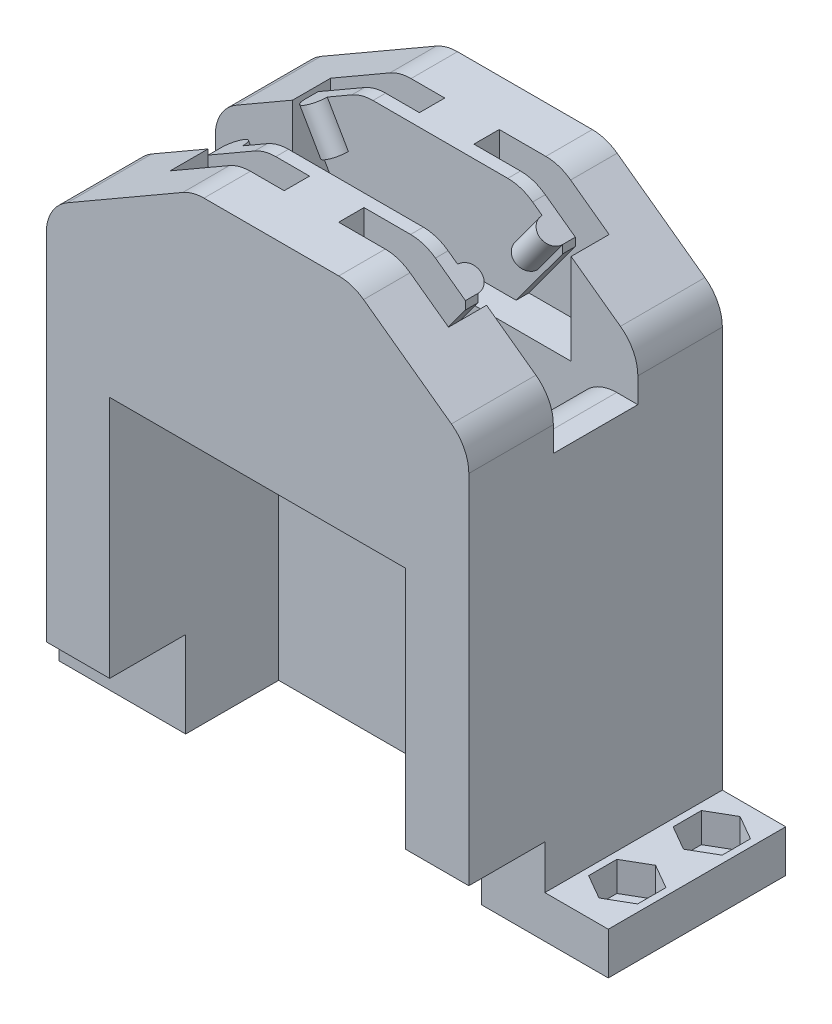
SolidWorks part; units mm, degrees
ref_plane "Front Plane" through (0, 0, 0) normal (0, 0, 1) x (1, 0, 0)
ref_plane "Top Plane" through (0, 0, 0) normal (0, 1, 0) x (1, 0, 0)
ref_plane "Right Plane" through (0, 0, 0) normal (1, 0, 0) x (0, 0, -1)
sketch "Sketch1" plane through (0, 0, 0) normal (0, 0, 1) x (1, 0, 0)
  line L0 (0.5834, 17.8723) -> (-16.7371, 7.8723)
  line L1 (-16.7371, 17.8723) -> (33.2629, 17.8723)
  line L2 (-16.7371, 17.8723) -> (-16.7371, -47.1277)
  line L3 (-16.7371, -47.1277) -> (33.2629, -47.1277)
  line L4 (33.2629, 17.8723) -> (33.2629, -47.1277)
  line L5 (19.4991, 17.8723) -> (33.2629, 7.8723)
  dimension "D1" = 50
  dimension "D2" = 65
  dimension "D3" = 0
  dimension "D4" = 0
  dimension "D5" = 60
  dimension "D6" = 0
  dimension "D7" = 0
  dimension "D8" = 54
  dimension "D9" = 10
  dimension "D10" = 10
extrude "Boss-Extrude1" add sketch "Sketch1" along normal blind 30 contours L5 L1 L0 L2 L3 L4 region at (8.347, -16.0926, 0)
sketch "Sketch2" plane through (0, 17.8723, 0) normal (0, 1, 0) x (1, 0, 0)
  line L0 (0.5834, 0) -> (19.4991, 0) construction
  line L1 (-16.7371, -10) -> (33.2629, -10)
  line L2 (-16.7371, -10) -> (-16.7371, -20)
  line L3 (-16.7371, -20) -> (33.2629, -20)
  line L4 (33.2629, -10) -> (33.2629, -20)
  line L5 (0.5834, -30) -> (19.4991, -30) construction
  line L6 (33.2629, -30) -> (33.2629, 0) construction
  line L7 (-16.7371, -30) -> (-16.7371, 0) construction
  dimension "D1" = 10
  dimension "D2" = 10
  dimension "D3" = 0
  dimension "D4" = 0
extrude "Cut-Extrude1" cut sketch "Sketch2" against normal blind 25
sketch "Sketch3" plane through (0, -47.1277, 0) normal (0, -1, 0) x (1, 0, 0)
  line L0 (-16.7371, 30) -> (33.2629, 30) construction
  line L1 (-9.2371, 20) -> (25.7629, 20)
  line L2 (-9.2371, 20) -> (-9.2371, 10)
  line L3 (-9.2371, 10) -> (25.7629, 10)
  line L4 (25.7629, 20) -> (25.7629, 10)
  line L5 (-16.7371, 0) -> (33.2629, 0) construction
  line L6 (33.2629, 30) -> (33.2629, 0) construction
  line L7 (-16.7371, 30) -> (-16.7371, 0) construction
  dimension "D1" = 10
  dimension "D2" = 10
  dimension "D3" = 7.5
  dimension "D4" = 7.5
sketch "Sketch4" plane through (-7.5931, 13.1516, 0) normal (-0.5, 0.866, 0) x (0, 0, 1)
  line L0 (10, -10.5586) -> (10, 9.4414) construction
  line L1 (10, -10.5586) -> (0, -10.5586) construction
  line L2 (20, 9.4414) -> (20, -10.5586) construction
  line L3 (30, -10.5586) -> (20, -10.5586) construction
  circle A0 centre (10, 3.2414) radius 1.5
  circle A1 centre (20, 3.2414) radius 1.5
  dimension "D2" = 13.8
  dimension "D5" = 3
  dimension "D6" = 13.8
  dimension "D1" = 0
  dimension "D3" = 0
extrude "Boss-Extrude2" add sketch "Sketch4" against normal blind 5
sketch "Sketch6" plane through (0, 17.8723, 0) normal (0, 1, 0) x (1, 0, 0)
  line L0 (19.4991, -10) -> (0.5834, -10) construction
  line L1 (-6.085, -5.5) -> (5.915, -5.5)
  line L2 (-6.085, -5.5) -> (-6.085, -8.5)
  line L3 (-6.085, -8.5) -> (5.915, -8.5)
  line L4 (5.915, -5.5) -> (5.915, -8.5)
  line L5 (-16.7371, -10) -> (-6.085, -10) construction
  line L6 (-6.085, -5.5) -> (-7.585, -5.5)
  line L7 (-6.085, -5.5) -> (-6.085, -10)
  line L8 (-6.085, -10) -> (-7.585, -10)
  line L9 (-7.585, -5.5) -> (-7.585, -10)
  line L10 (-6.085, -20) -> (-16.7371, -20) construction
  line L11 (-6.085, -21.5) -> (5.915, -21.5)
  line L12 (-6.085, -21.5) -> (-6.085, -24.5)
  line L13 (-6.085, -24.5) -> (5.915, -24.5)
  line L14 (5.915, -21.5) -> (5.915, -24.5)
  line L15 (-7.585, -20) -> (-6.085, -20)
  line L16 (-7.585, -20) -> (-7.585, -24.5)
  line L17 (-7.585, -24.5) -> (-6.085, -24.5)
  line L18 (-6.085, -20) -> (-6.085, -24.5)
  line L19 (0.5834, -20) -> (19.4991, -20) construction
  line M8 (0.5834, 0) -> (0.5834, -10)
  dimension "D1" = 0
  dimension "D2" = 3
  dimension "D3" = 12
  dimension "D4" = 1.5
  dimension "D5" = 0
  dimension "D6" = 0
  dimension "D7" = 1.5
  dimension "D8" = 0
  dimension "D9" = 0
  dimension "D10" = 0
  dimension "D11" = 1.5
  dimension "D12" = 0
  dimension "D13" = 0
  dimension "D14" = 1.5
  dimension "D15" = 3
  dimension "D16" = 12
extrude "Cut-Extrude15" cut sketch "Sketch6" against normal blind 15 contours L4 L1 L3 M8 | L2 L3 L1 M8 | L14 L11 L12 L13 | L18 L15 L16 L17 L12 | L9 L8 L7 L6 region at (-2.7508, 17.8723, 7) region at (3.2492, 17.8723, 7) region at (-0.085, 17.8723, 23) region at (-6.835, 17.8723, 22.25)
sketch "Sketch7" plane through (0, 0, 10) normal (0, 0, 1) x (1, 0, 0)
  line L0 (-6.085, 2.8723) -> (-7.585, 2.8723) construction
  line L1 (-6.085, 5.8723) -> (24.415, 5.8723)
  line L2 (-6.085, 5.8723) -> (-6.085, 2.8723)
  line L3 (-6.085, 2.8723) -> (24.415, 2.8723)
  line L4 (24.415, 5.8723) -> (24.415, 2.8723)
  line L6 (-6.085, 2.8723) -> (-6.085, 14.0223) construction
  dimension "D1" = 0
  dimension "D2" = 0
  dimension "D3" = 3
  dimension "D4" = 30.5
extrude "Cut-Extrude16" cut sketch "Sketch7" against normal blind 3 and the other way blind 13
sketch "Sketch8" plane through (0, 0, 30) normal (0, 0, 1) x (1, 0, 0)
  line L0 (-16.7371, -47.1277) -> (33.2629, -47.1277) construction
  line L1 (-9.2371, -8.1277) -> (25.7629, -8.1277)
  line L2 (-9.2371, -8.1277) -> (-9.2371, -47.1277)
  line L3 (-9.2371, -47.1277) -> (25.7629, -47.1277)
  line L4 (25.7629, -8.1277) -> (25.7629, -47.1277)
  line L5 (33.2629, 7.8723) -> (33.2629, -47.1277) construction
  line L6 (-16.7371, 7.8723) -> (-16.7371, -47.1277) construction
  point P6 (33.2629, -19.6277)
  dimension "D1" = 0
  dimension "D2" = 39
  dimension "D3" = 7.5
  dimension "D4" = 7.5
extrude "Cut-Extrude17" cut sketch "Sketch8" against normal up to surface (10 mm away) up to face at (4.4377, 7.8872, 20)
sketch "Sketch9" plane through (0, 0, 10) normal (0, 0, 1) x (1, 0, 0)
  line L1 (25.7629, -47.1277) -> (-9.2371, -47.1277) construction
  circle A0 centre (6.8891, -17.1277) radius 11.05
  dimension "D1" = 22.1
  dimension "D2" = 30
extrude "Cut-Extrude18" cut sketch "Sketch3" against normal up to surface (40 mm away) up to face at (8.2629, -7.1277, 15)
extrude "Cut-Extrude19" cut sketch "Sketch9" against normal blind 8
fillet "Fillet5" radius 5 1 edges at (-16.7371, 7.8723, 5) type face fillet first side face at (-7.9129, 12.9669, 5.1667) second side face at (-16.7371, -9.6277, 15)
fillet "Fillet6" radius 5 1 edges at (-16.7371, 7.8723, 25) type face fillet first side face at (-7.9129, 12.9669, 24.8333) second side face at (-16.7371, -10.3494, 15)
fillet "Fillet7" radius 5 1 edges at (0.5834, 17.8723, 2.75) type face fillet first side face at (-7.0795, 13.4481, 5.1667) second side face at (6.312, 17.8723, 6)
fillet "Fillet8" radius 5 1 edges at (0.5834, 17.8723, 9.25) type face fillet first side face at (-2.898, 15.8623, 9.7) second side face at (6.647, 17.8723, 6)
fillet "Fillet9" radius 5 1 edges at (0.5834, 17.8723, 20.75) type face fillet first side face at (-2.898, 15.8623, 20.3) second side face at (6.6452, 17.8723, 24)
fillet "Fillet10" radius 5 1 edges at (0.5834, 17.8723, 27.25) type face fillet first side face at (-7.0795, 13.4481, 24.8333) second side face at (6.9802, 17.8723, 24)
sketch "Sketch10" plane through (33.2629, 0, 0) normal (1, 0, 0) x (0, 0, -1)
  line L0 (-30, -47.1277) -> (0, -47.1277) construction
  line L1 (-30, -36.9277) -> (-21, -36.9277)
  line L2 (-30, -36.9277) -> (-30, -47.1277)
  line L3 (-30, -47.1277) -> (-21, -47.1277)
  line L4 (-21, -36.9277) -> (-21, -47.1277)
  line L5 (-30, 7.8723) -> (-30, -47.1277) construction
  dimension "D1" = 0
  dimension "D2" = 0
  dimension "D3" = 9
  dimension "D4" = 10.2
extrude "Cut-Extrude20" cut sketch "Sketch10" against normal through all
sketch "Sketch11" plane through (15.2355, 20.9699, 0) normal (0.5878, 0.809, 0) x (0, 0, -1)
  line L0 (-20, -5.27) -> (-20, -22.2831) construction
  line L1 (-10, -22.2831) -> (-10, -5.27) construction
  line L2 (-10, -22.2831) -> (0, -22.2831) construction
  line L3 (-30, -22.2831) -> (-20, -22.2831) construction
  circle A0 centre (-20, -9.7831) radius 1.5
  circle A1 centre (-10, -9.7831) radius 1.5
  dimension "D2" = 3
  dimension "D4" = 3
  dimension "D6" = 12.5
  dimension "D1" = 0
  dimension "D3" = 0
  dimension "D5" = 12.5
extrude "Boss-Extrude3" add sketch "Sketch11" against normal blind 5
sketch "Sketch13" plane through (0, 17.8723, 0) normal (0, 1, 0) x (1, 0, 0)
  line L1 (12.3637, -24.5) -> (24.3637, -24.5)
  line L2 (12.3637, -24.5) -> (12.3637, -21.5)
  line L3 (12.3637, -21.5) -> (24.3637, -21.5)
  line L4 (24.3637, -24.5) -> (24.3637, -21.5)
  line L5 (24.3637, -24.5) -> (25.3637, -24.5)
  line L6 (24.3637, -24.5) -> (24.3637, -14.9293)
  line L7 (24.3637, -14.9293) -> (25.3637, -14.9293)
  line L8 (25.3637, -24.5) -> (25.3637, -14.9293)
  line L9 (12.3637, -8.5) -> (24.3637, -8.5)
  line L10 (12.3637, -8.5) -> (12.3637, -5.5)
  line L11 (12.3637, -5.5) -> (24.3637, -5.5)
  line L12 (24.3637, -8.5) -> (24.3637, -5.5)
  line L13 (24.3637, -11.2788) -> (25.3637, -11.2788)
  line L14 (24.3637, -11.2788) -> (24.3637, -5.5)
  line L15 (24.3637, -5.5) -> (25.3637, -5.5)
  line L16 (25.3637, -11.2788) -> (25.3637, -5.5)
  line L17 (1.9232, -20) -> (19.4991, -20) construction
  line L18 (19.4991, -10) -> (1.9232, -10) construction
  line M4 (19.4991, -30) -> (19.4991, -20)
  dimension "D1" = 3
  dimension "D2" = 1.5
  dimension "D3" = 0
  dimension "D4" = 0
  dimension "D5" = 0
  dimension "D6" = 1
  dimension "D7" = 1
  dimension "D8" = 0
  dimension "D9" = 3
  dimension "D10" = 1.5
  dimension "D11" = 0
  dimension "D12" = 0
  dimension "D13" = 12
  dimension "D14" = 12
extrude "Cut-Extrude22" cut sketch "Sketch13" against normal blind 15 contours L3 L2 L1 M4 | L1 L4 L3 M4 | L5 L8 L7 L6 L4 | L13 L16 L15 L12 L14 | L9 L12 L11 L10 region at (15.9314, 17.8723, 23) region at (21.9314, 17.8723, 23) region at (24.8637, 17.8723, 19.7147) region at (18.3637, 17.8723, 7) region at (24.8637, 17.8723, 8.3894)
sketch "Sketch14" plane through (-16.7371, 0, 0) normal (-1, 0, 0) x (0, 0, 1)
  line L0 (21, -47.1277) -> (21, -36.9277) construction
  line L1 (0, -42.1277) -> (21, -42.1277)
  line L2 (0, -42.1277) -> (0, -47.1277)
  line L3 (0, -47.1277) -> (21, -47.1277)
  line L4 (21, -42.1277) -> (21, -47.1277)
  line L5 (21, -47.1277) -> (0, -47.1277) construction
  line L6 (0, 4.9855) -> (0, -47.1277) construction
  dimension "D1" = 5
  dimension "D2" = 0
  dimension "D3" = 0
  dimension "D4" = 0
extrude "Boss-Extrude4" add sketch "Sketch14" along normal blind 7.5
sketch "Sketch15" plane through (33.2629, 0, 0) normal (1, 0, 0) x (0, 0, -1)
  line L0 (-21, -47.1277) -> (-21, -36.9277) construction
  line L1 (-21, -42.1277) -> (0, -42.1277)
  line L2 (-21, -42.1277) -> (-21, -47.1277)
  line L3 (-21, -47.1277) -> (0, -47.1277)
  line L4 (0, -42.1277) -> (0, -47.1277)
  line L5 (-21, -47.1277) -> (0, -47.1277) construction
  line L6 (0, 7.8723) -> (0, -47.1277) construction
  dimension "D1" = 0
  dimension "D2" = 0
  dimension "D3" = 0
  dimension "D4" = 5
extrude "Boss-Extrude5" add sketch "Sketch15" along normal blind 7.5
sketch "Sketch16" plane through (0, -42.1277, 0) normal (0, 1, 0) x (1, 0, 0)
  line L0 (40.7629, 0) -> (40.7629, -21) construction
  line L1 (37.0129, -11.6514) -> (34.1129, -13.3257)
  line L2 (34.1129, -13.3257) -> (34.1129, -16.6743)
  line L3 (34.1129, -16.6743) -> (37.0129, -18.3486)
  line L4 (37.0129, -18.3486) -> (39.9129, -16.6743)
  line L5 (39.9129, -16.6743) -> (39.9129, -13.3257)
  line L6 (39.9129, -13.3257) -> (37.0129, -11.6514)
  line L7 (37.0129, -1.6514) -> (34.1129, -3.3257)
  line L8 (34.1129, -3.3257) -> (34.1129, -6.6743)
  line L9 (34.1129, -6.6743) -> (37.0129, -8.3486)
  line L10 (37.0129, -8.3486) -> (39.9129, -6.6743)
  line L11 (39.9129, -6.6743) -> (39.9129, -3.3257)
  line L12 (39.9129, -3.3257) -> (37.0129, -1.6514)
  line L13 (40.7629, 0) -> (33.2629, 0) construction
  circle A0 centre (37.0129, -15) radius 2.9 construction
  circle A1 centre (37.0129, -5) radius 2.9 construction
  dimension "D3" = 5.8
  dimension "D4" = 5.8
  dimension "D7" = 5
  dimension "D8" = 10
  dimension "D1" = 0
  dimension "D2" = 0
  dimension "D5" = 3.75
  dimension "D6" = 3.75
extrude "Cut-Extrude23" cut sketch "Sketch16" against normal blind 3.5
sketch "Sketch17" plane through (0, -45.6277, 0) normal (0, 1, 0) x (1, 0, 0)
  line L1 (40.7629, 0) -> (40.7629, -21) construction
  line L2 (40.7629, 0) -> (33.2629, 0) construction
  circle A0 centre (37.0129, -15) radius 1.425
  circle A1 centre (37.0129, -5) radius 1.425
  dimension "D1" = 2.85
  dimension "D2" = 2.85
  dimension "D3" = 3.75
  dimension "D4" = 3.75
  dimension "D5" = 5
  dimension "D6" = 10
extrude "Cut-Extrude24" cut sketch "Sketch17" against normal through all
sketch "Sketch19" plane through (0, -7.1277, 0) normal (0, 1, 0) x (1, 0, 0)
  line L0 (-9.2371, -20) -> (-9.2371, -10) construction
  line L1 (-9.2371, -10) -> (-16.7371, -10)
  line L2 (-9.2371, -10) -> (-9.2371, -20)
  line L3 (-9.2371, -20) -> (-16.7371, -20)
  line L4 (-16.7371, -10) -> (-16.7371, -20)
  line L5 (33.2629, -10) -> (25.7629, -10)
  line L6 (33.2629, -10) -> (33.2629, -20)
  line L7 (33.2629, -20) -> (25.7629, -20)
  line L8 (25.7629, -10) -> (25.7629, -20)
  line L9 (-9.2371, -10) -> (-16.7371, -10) construction
  line L10 (-16.7371, -10) -> (-16.7371, -20) construction
  line L11 (-16.7371, -20) -> (-9.2371, -20) construction
  line L12 (33.2629, -10) -> (25.7629, -10) construction
  line L13 (33.2629, -20) -> (33.2629, -10) construction
  line L14 (25.7629, -10) -> (25.7629, -20) construction
  line L15 (25.7629, -20) -> (33.2629, -20) construction
  dimension "D1" = 0
  dimension "D2" = 0
  dimension "D3" = 0
  dimension "D4" = 0
  dimension "D5" = 0
  dimension "D6" = 0
  dimension "D7" = 0
  dimension "D8" = 0
extrude "Boss-Extrude7" add sketch "Sketch19" along normal blind 9.5
fillet "Fillet14" radius 5 1 edges at (-9.2371, 2.3723, 15) type face fillet first side face at (-12.9871, 2.3723, 15) second side face at (-9.2371, -22.4527, 20.25)
fillet "Fillet18" radius 5 1 edges at (25.7629, 2.3723, 15) type face fillet first side face at (29.5129, 2.3723, 15) second side face at (25.7629, -22.4527, 20.25)
fillet "Fillet19" radius 5 1 edges at (33.2629, 7.8723, 5) type face fillet first side face at (26.0419, 13.1186, 5.1667) second side face at (33.2629, -9.9477, 15.15)
fillet "Fillet20" radius 5 1 edges at (33.2629, 7.8723, 25) type face fillet first side face at (26.0419, 13.1186, 24.8333) second side face at (33.2629, -10.5846, 15.15)
fillet "Fillet21" radius 5 1 edges at (19.4991, 17.8723, 2.75) type face fillet first side face at (10.0209, 17.8723, 6.3333) second side face at (25.3549, 13.6178, 5.1667)
fillet "Fillet22" radius 5 1 edges at (19.4991, 17.8723, 9.25) type face fillet first side face at (9.7501, 17.8723, 6.3333) second side face at (21.9325, 16.1043, 9.7)
fillet "Fillet23" radius 5 1 edges at (19.4991, 17.8723, 27.25) type face fillet first side face at (10.1872, 17.8723, 23.6667) second side face at (25.3549, 13.6178, 24.8333)
fillet "Fillet24" radius 5 1 edges at (19.4991, 17.8723, 20.75) type face fillet first side face at (9.9164, 17.8723, 23.6667) second side face at (21.9325, 16.1043, 20.3)
sketch "Sketch20" plane through (0, -42.1277, 0) normal (0, 1, 0) x (1, 0, 0)
  line L0 (-24.2371, -21) -> (-16.7371, -21) construction
  line L1 (-24.2371, -21) -> (-24.2371, 0) construction
  circle A0 centre (-20.5371, -11) radius 1.375
  dimension "D1" = 2.75
  dimension "D2" = 10
  dimension "D3" = 3.7
extrude "Cut-Extrude25" cut sketch "Sketch20" against normal blind 10
sketch "Sketch21" plane through (0, 0, 2) normal (0, 0, 1) x (1, 0, 0)
  circle A0 centre (6.8891, -17.1277) radius 5.5
  circle A1 centre (6.8891, -17.1277) radius 11.05 construction
  dimension "D1" = 0
  dimension "D2" = 11
extrude "Cut-Extrude26" cut sketch "Sketch21" against normal blind 10
sketch "Sketch22" plane through (0, 0, 10) normal (0, 0, 1) x (1, 0, 0)
  line L0 (-6.085, 12.8723) -> (-6.085, 5.8723)
  line L1 (-6.085, 5.8723) -> (-2.085, 5.8723)
  line L2 (-2.085, 5.8723) -> (-6.085, 12.8723)
  line L3 (24.3637, 13.3723) -> (18.8637, 5.8723)
  line L4 (18.8637, 5.8723) -> (24.3637, 5.8723)
  line L5 (24.3637, 5.8723) -> (24.3637, 13.3723)
  line L8 (-6.085, 5.8723) -> (-6.085, 14.0223) construction
  line L11 (24.3637, 14.3379) -> (24.3637, 5.8723) construction
  line L12 (24.3637, 5.8723) -> (-6.085, 5.8723) construction
  line M9 (-6.085, 14.0223) -> (-6.085, 5.8723)
  line M10 (-6.085, 5.8723) -> (24.3637, 5.8723)
  line M11 (24.3637, 5.8723) -> (24.3637, 14.3379)
  dimension "D1" = 0
  dimension "D2" = 7
  dimension "D3" = 0
  dimension "D4" = 4
  dimension "D5" = 0
  dimension "D6" = 0
  dimension "D7" = 7.5
  dimension "D8" = 5.5
extrude "Cut-Extrude27" cut sketch "Sketch22" against normal blind 3 and the other way blind 14 contours L2 M10 M9 | L3 M11 M10 region at (-4.7516, 8.2056, 10) region at (22.5304, 8.3723, 10)
